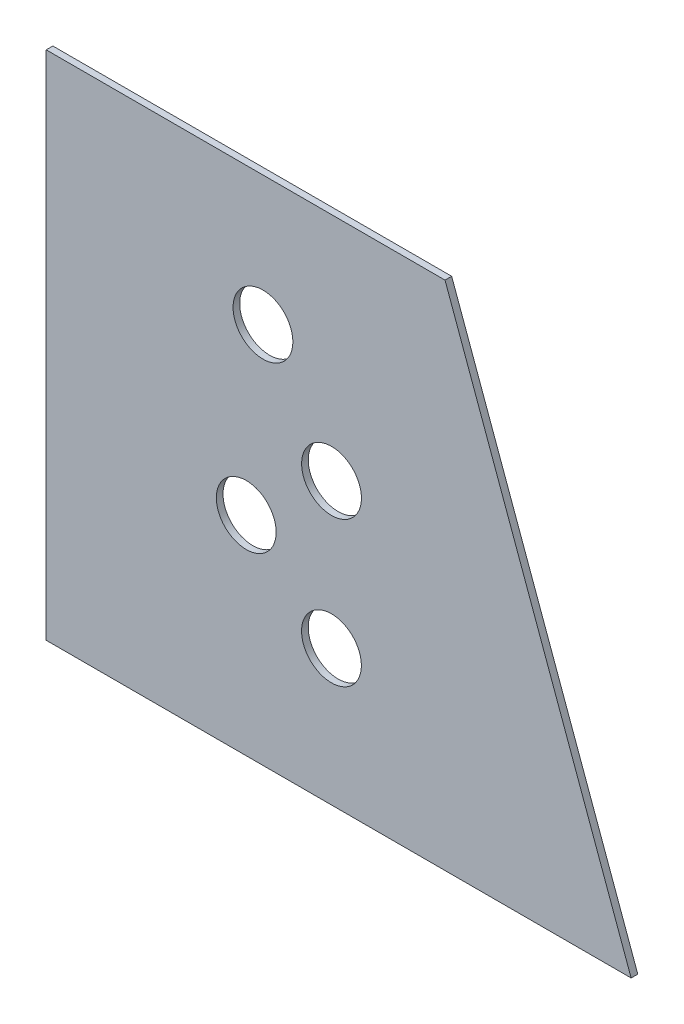
SolidWorks part; units mm, degrees
ref_plane "Front Plane" through (0, 0, 0) normal (0, 0, 1) x (1, 0, 0)
ref_plane "Top Plane" through (0, 0, 0) normal (0, 1, 0) x (1, 0, 0)
ref_plane "Right Plane" through (0, 0, 0) normal (1, 0, 0) x (0, 0, -1)
sketch "Sketch1" plane through (0, 0, 0) normal (0, 0, 1) x (1, 0, 0)
  line B0 (-0.1439, 244.2507) -> (190.3561, 244.2507)
  line B1 (190.3561, 244.2507) -> (279.2561, 0)
  line B2 (279.2561, 0) -> (-0.1439, 0)
  line B3 (-0.1439, 0) -> (-0.1439, 244.2507)
  circle B4 centre (103.3883, 182.3706) radius 14.2875
  circle B5 centre (136.1372, 134.0708) radius 14.2875
  circle B6 centre (95.4042, 99.6001) radius 14.2875
  circle B7 centre (136.1098, 64.8068) radius 14.2875
sketch_block_instance "Block-Gearbox_Plate2-1"
sketch_block "Block-Gearbox_Plate2" parameters "D3"=28.575, "D4"=28.575, "D5"=28.575, "D6"=28.575, "D1"=190.5, "D2"=279.4
extrude "Boss-Extrude1" add sketch "Sketch1" along normal blind 3.175
